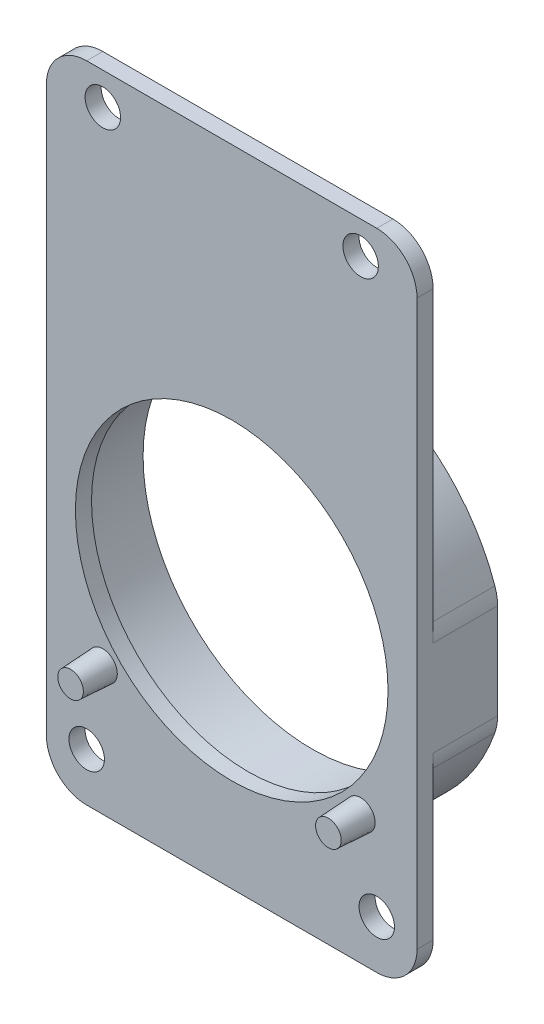
SolidWorks part; units mm, degrees
ref_plane "前视基准面" through (0, 0, 0) normal (0, 0, 1) x (1, 0, 0)
ref_plane "上视基准面" through (0, 0, 0) normal (0, 1, 0) x (1, 0, 0)
ref_plane "右视基准面" through (0, 0, 0) normal (1, 0, 0) x (0, 0, -1)
ref_axis "基准轴1" through (0, 0, 0) along (0, 0, 1)
sketch "草图1" plane through (0, 0, 0) normal (0, 0, 1) x (1, 0, 0)
  line L0 (0, -15.5) -> (0, 0) construction
  line L1 (-11.5, -15.5) -> (11.5, -15.5)
  line L2 (-11.5, -15.5) -> (-11.5, 24.5)
  line L3 (-11.5, 24.5) -> (11.5, 24.5)
  line L4 (11.5, -15.5) -> (11.5, 24.5)
  dimension "D1" = 15.5
  dimension "D2" = 40
  dimension "D3" = 23
extrude "凸台-拉伸1" add sketch "草图1" along normal blind 1
sketch "草图2" plane through (0, 0, 1) normal (0, 0, 1) x (1, 0, 0)
  circle A0 centre (0, 0) radius 9.7
  dimension "D1" = 19.4
extrude "切除-拉伸1" cut sketch "草图2" against normal through all
fillet "圆角1" radius 2.5 4 edges at (-11.5, 24.5, 0.5) (11.5, 24.5, 0.5) (11.5, -15.5, 0.5) (-11.5, -15.5, 0.5)
hole_wizard "M2 间隙孔1" positions "草图5" profile "草图6" hole size "M2" standard "GB" end condition through all
sketch "草图5" plane through (0, 0, 1) normal (0, 0, 1) x (1, 0, 0)
  line L1 (-8, 22.5) -> (8, 22.5)
  line L2 (-8, 22.5) -> (-9, -12.5)
  line L3 (-9, -12.5) -> (9, -12.5)
  line L4 (8, 22.5) -> (9, -12.5)
  line L5 (0, 0) -> (0, 22.5) construction
  point P0 (-8, 22.5)
  point P2 (8, 22.5)
  point P4 (-9, -12.5)
  point P6 (9, -12.5)
  dimension "D1" = 22.5
  dimension "D2" = 16
  dimension "D3" = 18
  dimension "D4" = 35
sketch "草图6" plane through (-8, 22.5, 1) normal (1, 0, 0) x (0, -1, 0)
  line L0 (0, 0) -> (0, 1)
  line L1 (0, 1) -> (1.1, 1)
  line L2 (1.1, 1) -> (1.1, 0)
  line L5 (1.1, 0) -> (0, 0)
  line L11 (0, -6.35) -> (0, 107.95) construction
  dimension "通孔孔直径" = 2.2
  dimension "通孔孔深度" = 1
sketch "草图7" plane through (0, 0, 1) normal (0, 0, 1) x (1, 0, 0)
  line L0 (-8, -7.5) -> (8, -7.5) construction
  line L1 (0, 0) -> (0, -7.5) construction
  circle A0 centre (-8, -7.5) radius 0.9
  circle A1 centre (8, -7.5) radius 0.9
  dimension "D3" = 1.8
  dimension "D1" = 7.5
  dimension "D2" = 16
extrude "凸台-拉伸2" add sketch "草图7" along normal blind 2 draft 3
sketch "草图8" plane through (0, 0, 0) normal (0, 0, -1) x (-1, 0, 0)
  line L0 (11.5, 3.4278) -> (11.5, -3.4278)
  line L1 (11.5, 22) -> (11.5, -13) construction
  line L2 (-11.5, 3.4278) -> (-11.5, -3.4278)
  line L3 (-11.5, -13) -> (-11.5, 22) construction
  arc A0 (11.5, 3.4278) -> (-11.5, 3.4278) centre (0, 0) ccw
  arc A1 (11.5, -3.4278) -> (11.5, 3.4278) centre (0, 0) ccw construction
  arc A2 (-11.5, 3.4278) -> (-11.5, -3.4278) centre (0, 0) ccw construction
  arc A3 (-11.5, -3.4278) -> (11.5, -3.4278) centre (0, 0) ccw
  circle A4 centre (0, 0) radius 10.5
  dimension "D1" = 24
  dimension "D2" = 21
extrude "凸台-拉伸3" add sketch "草图8" along normal blind 4
fillet "圆角2" radius 3 4 edges at (-11.5, -3.4278, -2) (-11.5, 3.4278, -2) (11.5, -3.4278, -2) (11.5, 3.4278, -2)
